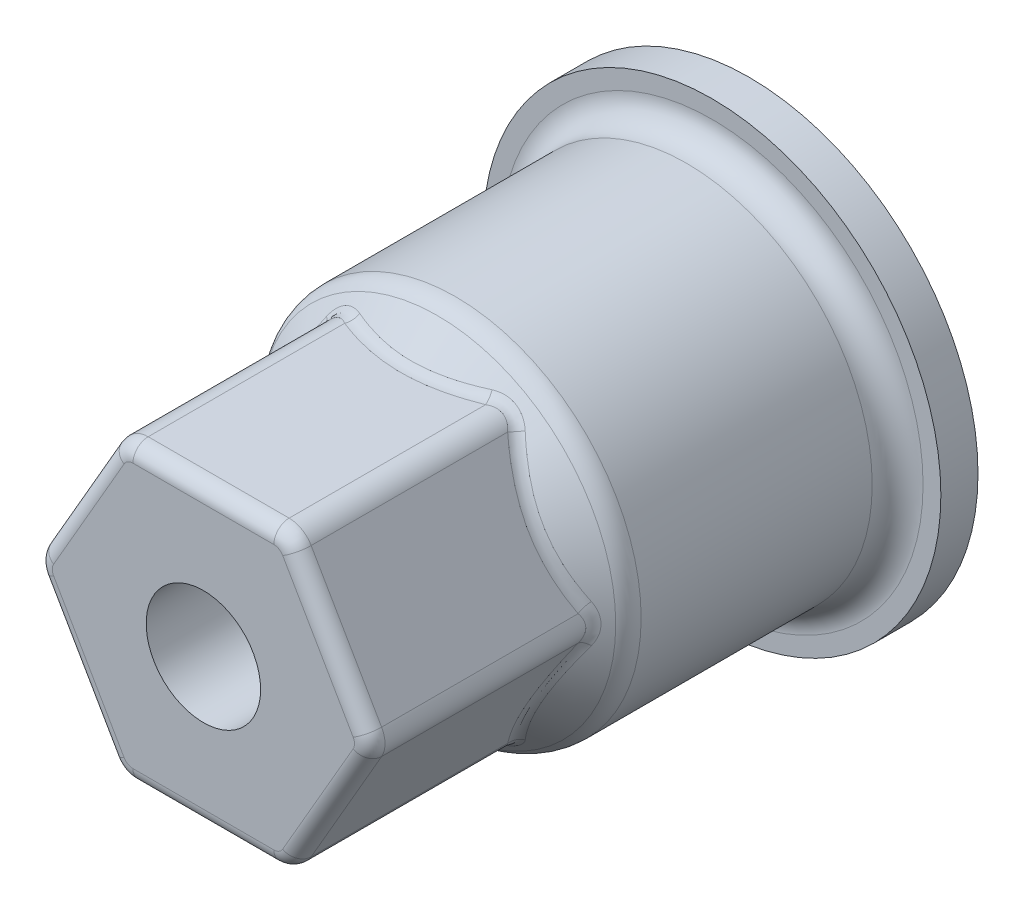
SolidWorks part; units mm, degrees
ref_plane "Front Plane" through (0, 0, 0) normal (0, 0, 1) x (1, 0, 0)
ref_plane "Top Plane" through (0, 0, 0) normal (0, 1, 0) x (1, 0, 0)
ref_plane "Right Plane" through (0, 0, 0) normal (1, 0, 0) x (0, 0, -1)
ref_plane "Plane1" through (0, 0, 0) normal (0, -1, 0) x (1, 0, 0)
sketch "Sketch1" plane through (0, 0, 0) normal (0, -1, 0) x (1, 0, 0)
  line L0 (7.3, 23.5) -> (0, 30.8)
  line L1 (0, 30.8) -> (0, 11.54)
  line L2 (0, 11.54) -> (9, 11.54)
  line L3 (9, 11.54) -> (9, 13)
  line L4 (9, 13) -> (7.3, 13)
  line L5 (7.3, 13) -> (7.3, 23.5)
  line L6 (0, 30.8) -> (0, 11.54) construction
revolve "Revolve1" add sketch "Sketch1" angle 360 about L6 reverse direction yes
ref_plane "Plane2" through (0, 0, 33) normal (0, 0, 1) x (1, 0, 0)
sketch "Sketch2" plane through (0, 0, 33) normal (0, 0, 1) x (1, 0, 0)
  line L0 (3.3486, 5.8) -> (-3.3486, 5.8)
  line L1 (-3.3486, 5.8) -> (-6.6973, 0)
  line L2 (-6.6973, 0) -> (-3.3486, -5.8)
  line L3 (-3.3486, -5.8) -> (3.3486, -5.8)
  line L4 (3.3486, -5.8) -> (6.6973, 0)
  line L5 (6.6973, 0) -> (3.3486, 5.8)
extrude "Boss-Extrude1" add sketch "Sketch2" against normal up to next
sketch "Sketch3" plane through (0, 0, 11.54) normal (0, 0, -1) x (-1, 0, 0)
  line L0 (-3.7, -2.1362) -> (0, -4.2724)
  line L1 (0, -4.2724) -> (3.7, -2.1362)
  line L2 (3.7, -2.1362) -> (3.7, 2.1362)
  line L3 (3.7, 2.1362) -> (0, 4.2724)
  line L4 (0, 4.2724) -> (-3.7, 2.1362)
  line L5 (-3.7, 2.1362) -> (-3.7, -2.1362)
extrude "Cut-Extrude1" cut sketch "Sketch3" against normal blind 3.66
hole_wizard "Ø4.5 (4.5) Diameter Hole1" positions "Sketch5" profile "Sketch4" hole size "Ø4.5" standard "ANSI Metric"
sketch "Sketch5" plane through (0, 0, 33) normal (0, 0, 1) x (1, 0, 0)
  point P0 (0, 0)
sketch "Sketch4" plane through (0, 0, 33) normal (1, 0, 0) x (0, -1, 0)
  line L0 (0, 0) -> (0, 17.6)
  line L1 (0, 17.6) -> (2.25, 17.6)
  line L2 (2.25, 17.6) -> (2.25, 0)
  line L5 (2.25, 0) -> (0, 0)
  line L10 (0, 17.6) -> (-2.25, 17.6) construction
  line L11 (0, -6.35) -> (0, 107.95) construction
  dimension "Hole Dia." = 4.5
  dimension "Hole Depth" = 17.6
  dimension "Drill Angle" = 180
fillet "Fillet1" radius 1 8 edges at (-7.3, 0, 13) (-7.3, 0, 23.5) (-3.3486, -5.8, 28.5514) (6.6973, 0, 28.5514) (3.3486, 5.8, 28.5514) (3.3486, -5.8, 28.5514) (-6.6973, 0, 28.5514) (-3.3486, 5.8, 28.5514) tangent propagation no
fillet "Fillet2" radius 0.6 24 edges at (6.5423, -0.0221, 24.2576) (5.2332, -2.5358, 24.9848) (4.8127, 3.2642, 24.9848) (3.252, -5.6769, 24.2576) (3.2903, 5.6548, 24.2576) (-0.2944, -5.8, 24.9925) (0.2944, 5.8, 24.9925) (-3.2903, -5.6548, 24.2576) (-3.252, 5.6769, 24.2576) (-4.8127, -3.2642, 24.9848) (-5.2332, 2.5358, 24.9848) (-6.5423, 0.0221, 24.2576) (3.2713, -5.666, 33) (0, -5.8, 33) (5.0229, -2.9, 33) (-3.2713, -5.666, 33) (6.5426, 0, 33) (-5.0229, -2.9, 33) (5.0229, 2.9, 33) (-6.5426, 0, 33) (3.2713, 5.666, 33) (-5.0229, 2.9, 33) (0, 5.8, 33) (-3.2713, 5.666, 33) tangent propagation no
